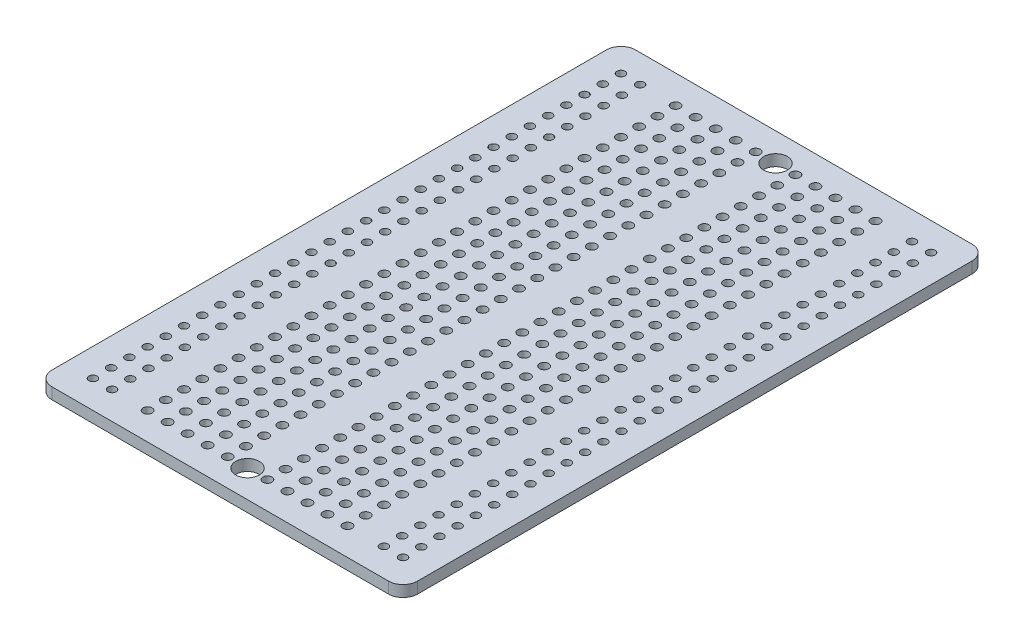
SolidWorks part; units mm, degrees
ref_plane "Front Plane" through (0, 0, 0) normal (0, 0, 1) x (1, 0, 0)
ref_plane "Top Plane" through (0, 0, 0) normal (0, 1, 0) x (1, 0, 0)
ref_plane "Right Plane" through (0, 0, 0) normal (1, 0, 0) x (0, 0, -1)
sketch "Sketch1" plane through (0, 0, 0) normal (0, 1, 0) x (1, 0, 0)
  line L1 (0, 0) -> (51.0032, 0)
  line L2 (0, 0) -> (0, 81.407)
  line L3 (0, 81.407) -> (51.0032, 81.407)
  line L4 (51.0032, 0) -> (51.0032, 81.407)
  dimension "D1" = 81.407
  dimension "D2" = 51.0032
extrude "Boss-Extrude1" add sketch "Sketch1" along normal blind 1.5748
fillet "Fillet1" radius 2.032 4 edges at (0, 0.7874, -81.407) (51.0032, 0.7874, -81.407) (0, 0.7874, 0) (51.0032, 0.7874, 0)
sketch "Sketch2" plane through (0, 1.5748, 0) normal (0, 1, 0) x (1, 0, 0)
  line L0 (3.302, 81.407) -> (3.302, 0) construction
  line L1 (48.9712, 81.407) -> (2.032, 81.407) construction
  line L2 (2.032, 0) -> (48.9712, 0) construction
  line L3 (4.445, 81.407) -> (4.445, 0) construction
  line L4 (5.969, 81.407) -> (5.969, 0) construction
  line L5 (7.112, 81.407) -> (7.112, 0) construction
  line L6 (10.922, 81.407) -> (10.922, 0) construction
  line L7 (12.192, 81.407) -> (12.192, 0) construction
  line L8 (13.716, 81.407) -> (13.716, 0) construction
  line L9 (0, 79.375) -> (0, 2.032) construction
  line L10 (0, 78.105) -> (51.0032, 78.105) construction
  line L11 (51.0032, 2.032) -> (51.0032, 79.375) construction
  line L12 (11.557, 77.47) -> (14.351, 77.47) construction
  line L13 (25.5016, 81.407) -> (25.5016, 0) construction
  line L14 (3.8735, 77.5335) -> (3.8735, 74.9935) construction
  line L15 (25.5016, 5.588) -> (25.5016, 75.819) construction
  line L16 (23.368, 77.47) -> (27.6352, 77.47) construction
  circle A0 centre (3.8735, 77.5335) radius 0.5715
  circle A1 centre (6.5405, 77.5335) radius 0.5715
  circle A2 centre (11.557, 77.47) radius 0.635
  circle A3 centre (14.351, 77.47) radius 0.635
  circle A4 centre (17.145, 77.47) radius 0.635
  circle A5 centre (19.939, 77.47) radius 0.635
  circle A6 centre (22.733, 77.47) radius 0.635
  circle A7 centre (47.1297, 77.5335) radius 0.5715
  circle A8 centre (44.4627, 77.5335) radius 0.5715
  circle A9 centre (39.4462, 77.47) radius 0.635
  circle A10 centre (36.6522, 77.47) radius 0.635
  circle A11 centre (33.8582, 77.47) radius 0.635
  circle A12 centre (31.0642, 77.47) radius 0.635
  circle A13 centre (28.2702, 77.47) radius 0.635
  circle A14 centre (3.8735, 74.9935) radius 0.5715
  circle A15 centre (6.5405, 74.9935) radius 0.5715
  circle A16 centre (11.557, 74.93) radius 0.635
  circle A17 centre (14.351, 74.93) radius 0.635
  circle A18 centre (17.145, 74.93) radius 0.635
  circle A19 centre (19.939, 74.93) radius 0.635
  circle A20 centre (22.733, 74.93) radius 0.635
  circle A21 centre (28.2702, 74.93) radius 0.635
  circle A22 centre (31.0642, 74.93) radius 0.635
  circle A23 centre (33.8582, 74.93) radius 0.635
  circle A24 centre (36.6522, 74.93) radius 0.635
  circle A25 centre (39.4462, 74.93) radius 0.635
  circle A26 centre (44.4627, 74.9935) radius 0.5715
  circle A27 centre (47.1297, 74.9935) radius 0.5715
  circle A28 centre (3.8735, 72.4535) radius 0.5715
  circle A29 centre (6.5405, 72.4535) radius 0.5715
  circle A30 centre (11.557, 72.39) radius 0.635
  circle A31 centre (14.351, 72.39) radius 0.635
  circle A32 centre (17.145, 72.39) radius 0.635
  circle A33 centre (19.939, 72.39) radius 0.635
  circle A34 centre (22.733, 72.39) radius 0.635
  circle A35 centre (28.2702, 72.39) radius 0.635
  circle A36 centre (31.0642, 72.39) radius 0.635
  circle A37 centre (33.8582, 72.39) radius 0.635
  circle A38 centre (36.6522, 72.39) radius 0.635
  circle A39 centre (39.4462, 72.39) radius 0.635
  circle A40 centre (44.4627, 72.4535) radius 0.5715
  circle A41 centre (47.1297, 72.4535) radius 0.5715
  circle A42 centre (3.8735, 69.9135) radius 0.5715
  circle A43 centre (6.5405, 69.9135) radius 0.5715
  circle A44 centre (11.557, 69.85) radius 0.635
  circle A45 centre (14.351, 69.85) radius 0.635
  circle A46 centre (17.145, 69.85) radius 0.635
  circle A47 centre (19.939, 69.85) radius 0.635
  circle A48 centre (22.733, 69.85) radius 0.635
  circle A49 centre (28.2702, 69.85) radius 0.635
  circle A50 centre (31.0642, 69.85) radius 0.635
  circle A51 centre (33.8582, 69.85) radius 0.635
  circle A52 centre (36.6522, 69.85) radius 0.635
  circle A53 centre (39.4462, 69.85) radius 0.635
  circle A54 centre (44.4627, 69.9135) radius 0.5715
  circle A55 centre (47.1297, 69.9135) radius 0.5715
  circle A56 centre (3.8735, 67.3735) radius 0.5715
  circle A57 centre (6.5405, 67.3735) radius 0.5715
  circle A58 centre (11.557, 67.31) radius 0.635
  circle A59 centre (14.351, 67.31) radius 0.635
  circle A60 centre (17.145, 67.31) radius 0.635
  circle A61 centre (19.939, 67.31) radius 0.635
  circle A62 centre (22.733, 67.31) radius 0.635
  circle A63 centre (28.2702, 67.31) radius 0.635
  circle A64 centre (31.0642, 67.31) radius 0.635
  circle A65 centre (33.8582, 67.31) radius 0.635
  circle A66 centre (36.6522, 67.31) radius 0.635
  circle A67 centre (39.4462, 67.31) radius 0.635
  circle A68 centre (44.4627, 67.3735) radius 0.5715
  circle A69 centre (47.1297, 67.3735) radius 0.5715
  circle A70 centre (3.8735, 64.8335) radius 0.5715
  circle A71 centre (6.5405, 64.8335) radius 0.5715
  circle A72 centre (11.557, 64.77) radius 0.635
  circle A73 centre (14.351, 64.77) radius 0.635
  circle A74 centre (17.145, 64.77) radius 0.635
  circle A75 centre (19.939, 64.77) radius 0.635
  circle A76 centre (22.733, 64.77) radius 0.635
  circle A77 centre (28.2702, 64.77) radius 0.635
  circle A78 centre (31.0642, 64.77) radius 0.635
  circle A79 centre (33.8582, 64.77) radius 0.635
  circle A80 centre (36.6522, 64.77) radius 0.635
  circle A81 centre (39.4462, 64.77) radius 0.635
  circle A82 centre (44.4627, 64.8335) radius 0.5715
  circle A83 centre (47.1297, 64.8335) radius 0.5715
  circle A84 centre (3.8735, 62.2935) radius 0.5715
  circle A85 centre (6.5405, 62.2935) radius 0.5715
  circle A86 centre (11.557, 62.23) radius 0.635
  circle A87 centre (14.351, 62.23) radius 0.635
  circle A88 centre (17.145, 62.23) radius 0.635
  circle A89 centre (19.939, 62.23) radius 0.635
  circle A90 centre (22.733, 62.23) radius 0.635
  circle A91 centre (28.2702, 62.23) radius 0.635
  circle A92 centre (31.0642, 62.23) radius 0.635
  circle A93 centre (33.8582, 62.23) radius 0.635
  circle A94 centre (36.6522, 62.23) radius 0.635
  circle A95 centre (39.4462, 62.23) radius 0.635
  circle A96 centre (44.4627, 62.2935) radius 0.5715
  circle A97 centre (47.1297, 62.2935) radius 0.5715
  circle A98 centre (3.8735, 59.7535) radius 0.5715
  circle A99 centre (6.5405, 59.7535) radius 0.5715
  circle A100 centre (11.557, 59.69) radius 0.635
  circle A101 centre (14.351, 59.69) radius 0.635
  circle A102 centre (17.145, 59.69) radius 0.635
  circle A103 centre (19.939, 59.69) radius 0.635
  circle A104 centre (22.733, 59.69) radius 0.635
  circle A105 centre (28.2702, 59.69) radius 0.635
  circle A106 centre (31.0642, 59.69) radius 0.635
  circle A107 centre (33.8582, 59.69) radius 0.635
  circle A108 centre (36.6522, 59.69) radius 0.635
  circle A109 centre (39.4462, 59.69) radius 0.635
  circle A110 centre (44.4627, 59.7535) radius 0.5715
  circle A111 centre (47.1297, 59.7535) radius 0.5715
  circle A112 centre (3.8735, 57.2135) radius 0.5715
  circle A113 centre (6.5405, 57.2135) radius 0.5715
  circle A114 centre (11.557, 57.15) radius 0.635
  circle A115 centre (14.351, 57.15) radius 0.635
  circle A116 centre (17.145, 57.15) radius 0.635
  circle A117 centre (19.939, 57.15) radius 0.635
  circle A118 centre (22.733, 57.15) radius 0.635
  circle A119 centre (28.2702, 57.15) radius 0.635
  circle A120 centre (31.0642, 57.15) radius 0.635
  circle A121 centre (33.8582, 57.15) radius 0.635
  circle A122 centre (36.6522, 57.15) radius 0.635
  circle A123 centre (39.4462, 57.15) radius 0.635
  circle A124 centre (44.4627, 57.2135) radius 0.5715
  circle A125 centre (47.1297, 57.2135) radius 0.5715
  circle A126 centre (3.8735, 54.6735) radius 0.5715
  circle A127 centre (6.5405, 54.6735) radius 0.5715
  circle A128 centre (11.557, 54.61) radius 0.635
  circle A129 centre (14.351, 54.61) radius 0.635
  circle A130 centre (17.145, 54.61) radius 0.635
  circle A131 centre (19.939, 54.61) radius 0.635
  circle A132 centre (22.733, 54.61) radius 0.635
  circle A133 centre (28.2702, 54.61) radius 0.635
  circle A134 centre (31.0642, 54.61) radius 0.635
  circle A135 centre (33.8582, 54.61) radius 0.635
  circle A136 centre (36.6522, 54.61) radius 0.635
  circle A137 centre (39.4462, 54.61) radius 0.635
  circle A138 centre (44.4627, 54.6735) radius 0.5715
  circle A139 centre (47.1297, 54.6735) radius 0.5715
  circle A140 centre (3.8735, 52.1335) radius 0.5715
  circle A141 centre (6.5405, 52.1335) radius 0.5715
  circle A142 centre (11.557, 52.07) radius 0.635
  circle A143 centre (14.351, 52.07) radius 0.635
  circle A144 centre (17.145, 52.07) radius 0.635
  circle A145 centre (19.939, 52.07) radius 0.635
  circle A146 centre (22.733, 52.07) radius 0.635
  circle A147 centre (28.2702, 52.07) radius 0.635
  circle A148 centre (31.0642, 52.07) radius 0.635
  circle A149 centre (33.8582, 52.07) radius 0.635
  circle A150 centre (36.6522, 52.07) radius 0.635
  circle A151 centre (39.4462, 52.07) radius 0.635
  circle A152 centre (44.4627, 52.1335) radius 0.5715
  circle A153 centre (47.1297, 52.1335) radius 0.5715
  circle A154 centre (3.8735, 49.5935) radius 0.5715
  circle A155 centre (6.5405, 49.5935) radius 0.5715
  circle A156 centre (11.557, 49.53) radius 0.635
  circle A157 centre (14.351, 49.53) radius 0.635
  circle A158 centre (17.145, 49.53) radius 0.635
  circle A159 centre (19.939, 49.53) radius 0.635
  circle A160 centre (22.733, 49.53) radius 0.635
  circle A161 centre (28.2702, 49.53) radius 0.635
  circle A162 centre (31.0642, 49.53) radius 0.635
  circle A163 centre (33.8582, 49.53) radius 0.635
  circle A164 centre (36.6522, 49.53) radius 0.635
  circle A165 centre (39.4462, 49.53) radius 0.635
  circle A166 centre (44.4627, 49.5935) radius 0.5715
  circle A167 centre (47.1297, 49.5935) radius 0.5715
  circle A168 centre (3.8735, 47.0535) radius 0.5715
  circle A169 centre (6.5405, 47.0535) radius 0.5715
  circle A170 centre (11.557, 46.99) radius 0.635
  circle A171 centre (14.351, 46.99) radius 0.635
  circle A172 centre (17.145, 46.99) radius 0.635
  circle A173 centre (19.939, 46.99) radius 0.635
  circle A174 centre (22.733, 46.99) radius 0.635
  circle A175 centre (28.2702, 46.99) radius 0.635
  circle A176 centre (31.0642, 46.99) radius 0.635
  circle A177 centre (33.8582, 46.99) radius 0.635
  circle A178 centre (36.6522, 46.99) radius 0.635
  circle A179 centre (39.4462, 46.99) radius 0.635
  circle A180 centre (44.4627, 47.0535) radius 0.5715
  circle A181 centre (47.1297, 47.0535) radius 0.5715
  circle A182 centre (3.8735, 44.5135) radius 0.5715
  circle A183 centre (6.5405, 44.5135) radius 0.5715
  circle A184 centre (11.557, 44.45) radius 0.635
  circle A185 centre (14.351, 44.45) radius 0.635
  circle A186 centre (17.145, 44.45) radius 0.635
  circle A187 centre (19.939, 44.45) radius 0.635
  circle A188 centre (22.733, 44.45) radius 0.635
  circle A189 centre (28.2702, 44.45) radius 0.635
  circle A190 centre (31.0642, 44.45) radius 0.635
  circle A191 centre (33.8582, 44.45) radius 0.635
  circle A192 centre (36.6522, 44.45) radius 0.635
  circle A193 centre (39.4462, 44.45) radius 0.635
  circle A194 centre (44.4627, 44.5135) radius 0.5715
  circle A195 centre (47.1297, 44.5135) radius 0.5715
  circle A196 centre (3.8735, 41.9735) radius 0.5715
  circle A197 centre (6.5405, 41.9735) radius 0.5715
  circle A198 centre (11.557, 41.91) radius 0.635
  circle A199 centre (14.351, 41.91) radius 0.635
  circle A200 centre (17.145, 41.91) radius 0.635
  circle A201 centre (19.939, 41.91) radius 0.635
  circle A202 centre (22.733, 41.91) radius 0.635
  circle A203 centre (28.2702, 41.91) radius 0.635
  circle A204 centre (31.0642, 41.91) radius 0.635
  circle A205 centre (33.8582, 41.91) radius 0.635
  circle A206 centre (36.6522, 41.91) radius 0.635
  circle A207 centre (39.4462, 41.91) radius 0.635
  circle A208 centre (44.4627, 41.9735) radius 0.5715
  circle A209 centre (47.1297, 41.9735) radius 0.5715
  circle A210 centre (3.8735, 39.4335) radius 0.5715
  circle A211 centre (6.5405, 39.4335) radius 0.5715
  circle A212 centre (11.557, 39.37) radius 0.635
  circle A213 centre (14.351, 39.37) radius 0.635
  circle A214 centre (17.145, 39.37) radius 0.635
  circle A215 centre (19.939, 39.37) radius 0.635
  circle A216 centre (22.733, 39.37) radius 0.635
  circle A217 centre (28.2702, 39.37) radius 0.635
  circle A218 centre (31.0642, 39.37) radius 0.635
  circle A219 centre (33.8582, 39.37) radius 0.635
  circle A220 centre (36.6522, 39.37) radius 0.635
  circle A221 centre (39.4462, 39.37) radius 0.635
  circle A222 centre (44.4627, 39.4335) radius 0.5715
  circle A223 centre (47.1297, 39.4335) radius 0.5715
  circle A224 centre (3.8735, 36.8935) radius 0.5715
  circle A225 centre (6.5405, 36.8935) radius 0.5715
  circle A226 centre (11.557, 36.83) radius 0.635
  circle A227 centre (14.351, 36.83) radius 0.635
  circle A228 centre (17.145, 36.83) radius 0.635
  circle A229 centre (19.939, 36.83) radius 0.635
  circle A230 centre (22.733, 36.83) radius 0.635
  circle A231 centre (28.2702, 36.83) radius 0.635
  circle A232 centre (31.0642, 36.83) radius 0.635
  circle A233 centre (33.8582, 36.83) radius 0.635
  circle A234 centre (36.6522, 36.83) radius 0.635
  circle A235 centre (39.4462, 36.83) radius 0.635
  circle A236 centre (44.4627, 36.8935) radius 0.5715
  circle A237 centre (47.1297, 36.8935) radius 0.5715
  circle A238 centre (3.8735, 34.3535) radius 0.5715
  circle A239 centre (6.5405, 34.3535) radius 0.5715
  circle A240 centre (11.557, 34.29) radius 0.635
  circle A241 centre (14.351, 34.29) radius 0.635
  circle A242 centre (17.145, 34.29) radius 0.635
  circle A243 centre (19.939, 34.29) radius 0.635
  circle A244 centre (22.733, 34.29) radius 0.635
  circle A245 centre (28.2702, 34.29) radius 0.635
  circle A246 centre (31.0642, 34.29) radius 0.635
  circle A247 centre (33.8582, 34.29) radius 0.635
  circle A248 centre (36.6522, 34.29) radius 0.635
  circle A249 centre (39.4462, 34.29) radius 0.635
  circle A250 centre (44.4627, 34.3535) radius 0.5715
  circle A251 centre (47.1297, 34.3535) radius 0.5715
  circle A252 centre (3.8735, 31.8135) radius 0.5715
  circle A253 centre (6.5405, 31.8135) radius 0.5715
  circle A254 centre (11.557, 31.75) radius 0.635
  circle A255 centre (14.351, 31.75) radius 0.635
  circle A256 centre (17.145, 31.75) radius 0.635
  circle A257 centre (19.939, 31.75) radius 0.635
  circle A258 centre (22.733, 31.75) radius 0.635
  circle A259 centre (28.2702, 31.75) radius 0.635
  circle A260 centre (31.0642, 31.75) radius 0.635
  circle A261 centre (33.8582, 31.75) radius 0.635
  circle A262 centre (36.6522, 31.75) radius 0.635
  circle A263 centre (39.4462, 31.75) radius 0.635
  circle A264 centre (44.4627, 31.8135) radius 0.5715
  circle A265 centre (47.1297, 31.8135) radius 0.5715
  circle A266 centre (3.8735, 29.2735) radius 0.5715
  circle A267 centre (6.5405, 29.2735) radius 0.5715
  circle A268 centre (11.557, 29.21) radius 0.635
  circle A269 centre (14.351, 29.21) radius 0.635
  circle A270 centre (17.145, 29.21) radius 0.635
  circle A271 centre (19.939, 29.21) radius 0.635
  circle A272 centre (22.733, 29.21) radius 0.635
  circle A273 centre (28.2702, 29.21) radius 0.635
  circle A274 centre (31.0642, 29.21) radius 0.635
  circle A275 centre (33.8582, 29.21) radius 0.635
  circle A276 centre (36.6522, 29.21) radius 0.635
  circle A277 centre (39.4462, 29.21) radius 0.635
  circle A278 centre (44.4627, 29.2735) radius 0.5715
  circle A279 centre (47.1297, 29.2735) radius 0.5715
  circle A280 centre (3.8735, 26.7335) radius 0.5715
  circle A281 centre (6.5405, 26.7335) radius 0.5715
  circle A282 centre (11.557, 26.67) radius 0.635
  circle A283 centre (14.351, 26.67) radius 0.635
  circle A284 centre (17.145, 26.67) radius 0.635
  circle A285 centre (19.939, 26.67) radius 0.635
  circle A286 centre (22.733, 26.67) radius 0.635
  circle A287 centre (28.2702, 26.67) radius 0.635
  circle A288 centre (31.0642, 26.67) radius 0.635
  circle A289 centre (33.8582, 26.67) radius 0.635
  circle A290 centre (36.6522, 26.67) radius 0.635
  circle A291 centre (39.4462, 26.67) radius 0.635
  circle A292 centre (44.4627, 26.7335) radius 0.5715
  circle A293 centre (47.1297, 26.7335) radius 0.5715
  circle A294 centre (3.8735, 24.1935) radius 0.5715
  circle A295 centre (6.5405, 24.1935) radius 0.5715
  circle A296 centre (11.557, 24.13) radius 0.635
  circle A297 centre (14.351, 24.13) radius 0.635
  circle A298 centre (17.145, 24.13) radius 0.635
  circle A299 centre (19.939, 24.13) radius 0.635
  circle A300 centre (22.733, 24.13) radius 0.635
  circle A301 centre (28.2702, 24.13) radius 0.635
  circle A302 centre (31.0642, 24.13) radius 0.635
  circle A303 centre (33.8582, 24.13) radius 0.635
  circle A304 centre (36.6522, 24.13) radius 0.635
  circle A305 centre (39.4462, 24.13) radius 0.635
  circle A306 centre (44.4627, 24.1935) radius 0.5715
  circle A307 centre (47.1297, 24.1935) radius 0.5715
  circle A308 centre (3.8735, 21.6535) radius 0.5715
  circle A309 centre (6.5405, 21.6535) radius 0.5715
  circle A310 centre (11.557, 21.59) radius 0.635
  circle A311 centre (14.351, 21.59) radius 0.635
  circle A312 centre (17.145, 21.59) radius 0.635
  circle A313 centre (19.939, 21.59) radius 0.635
  circle A314 centre (22.733, 21.59) radius 0.635
  circle A315 centre (28.2702, 21.59) radius 0.635
  circle A316 centre (31.0642, 21.59) radius 0.635
  circle A317 centre (33.8582, 21.59) radius 0.635
  circle A318 centre (36.6522, 21.59) radius 0.635
  circle A319 centre (39.4462, 21.59) radius 0.635
  circle A320 centre (44.4627, 21.6535) radius 0.5715
  circle A321 centre (47.1297, 21.6535) radius 0.5715
  circle A322 centre (3.8735, 19.1135) radius 0.5715
  circle A323 centre (6.5405, 19.1135) radius 0.5715
  circle A324 centre (11.557, 19.05) radius 0.635
  circle A325 centre (14.351, 19.05) radius 0.635
  circle A326 centre (17.145, 19.05) radius 0.635
  circle A327 centre (19.939, 19.05) radius 0.635
  circle A328 centre (22.733, 19.05) radius 0.635
  circle A329 centre (28.2702, 19.05) radius 0.635
  circle A330 centre (31.0642, 19.05) radius 0.635
  circle A331 centre (33.8582, 19.05) radius 0.635
  circle A332 centre (36.6522, 19.05) radius 0.635
  circle A333 centre (39.4462, 19.05) radius 0.635
  circle A334 centre (44.4627, 19.1135) radius 0.5715
  circle A335 centre (47.1297, 19.1135) radius 0.5715
  circle A336 centre (3.8735, 16.5735) radius 0.5715
  circle A337 centre (6.5405, 16.5735) radius 0.5715
  circle A338 centre (11.557, 16.51) radius 0.635
  circle A339 centre (14.351, 16.51) radius 0.635
  circle A340 centre (17.145, 16.51) radius 0.635
  circle A341 centre (19.939, 16.51) radius 0.635
  circle A342 centre (22.733, 16.51) radius 0.635
  circle A343 centre (28.2702, 16.51) radius 0.635
  circle A344 centre (31.0642, 16.51) radius 0.635
  circle A345 centre (33.8582, 16.51) radius 0.635
  circle A346 centre (36.6522, 16.51) radius 0.635
  circle A347 centre (39.4462, 16.51) radius 0.635
  circle A348 centre (44.4627, 16.5735) radius 0.5715
  circle A349 centre (47.1297, 16.5735) radius 0.5715
  circle A350 centre (3.8735, 14.0335) radius 0.5715
  circle A351 centre (6.5405, 14.0335) radius 0.5715
  circle A352 centre (11.557, 13.97) radius 0.635
  circle A353 centre (14.351, 13.97) radius 0.635
  circle A354 centre (17.145, 13.97) radius 0.635
  circle A355 centre (19.939, 13.97) radius 0.635
  circle A356 centre (22.733, 13.97) radius 0.635
  circle A357 centre (28.2702, 13.97) radius 0.635
  circle A358 centre (31.0642, 13.97) radius 0.635
  circle A359 centre (33.8582, 13.97) radius 0.635
  circle A360 centre (36.6522, 13.97) radius 0.635
  circle A361 centre (39.4462, 13.97) radius 0.635
  circle A362 centre (44.4627, 14.0335) radius 0.5715
  circle A363 centre (47.1297, 14.0335) radius 0.5715
  circle A364 centre (3.8735, 11.4935) radius 0.5715
  circle A365 centre (6.5405, 11.4935) radius 0.5715
  circle A366 centre (11.557, 11.43) radius 0.635
  circle A367 centre (14.351, 11.43) radius 0.635
  circle A368 centre (17.145, 11.43) radius 0.635
  circle A369 centre (19.939, 11.43) radius 0.635
  circle A370 centre (22.733, 11.43) radius 0.635
  circle A371 centre (28.2702, 11.43) radius 0.635
  circle A372 centre (31.0642, 11.43) radius 0.635
  circle A373 centre (33.8582, 11.43) radius 0.635
  circle A374 centre (36.6522, 11.43) radius 0.635
  circle A375 centre (39.4462, 11.43) radius 0.635
  circle A376 centre (44.4627, 11.4935) radius 0.5715
  circle A377 centre (47.1297, 11.4935) radius 0.5715
  circle A378 centre (3.8735, 8.9535) radius 0.5715
  circle A379 centre (6.5405, 8.9535) radius 0.5715
  circle A380 centre (11.557, 8.89) radius 0.635
  circle A381 centre (14.351, 8.89) radius 0.635
  circle A382 centre (17.145, 8.89) radius 0.635
  circle A383 centre (19.939, 8.89) radius 0.635
  circle A384 centre (22.733, 8.89) radius 0.635
  circle A385 centre (28.2702, 8.89) radius 0.635
  circle A386 centre (31.0642, 8.89) radius 0.635
  circle A387 centre (33.8582, 8.89) radius 0.635
  circle A388 centre (36.6522, 8.89) radius 0.635
  circle A389 centre (39.4462, 8.89) radius 0.635
  circle A390 centre (44.4627, 8.9535) radius 0.5715
  circle A391 centre (47.1297, 8.9535) radius 0.5715
  circle A392 centre (3.8735, 6.4135) radius 0.5715
  circle A393 centre (6.5405, 6.4135) radius 0.5715
  circle A394 centre (11.557, 6.35) radius 0.635
  circle A395 centre (14.351, 6.35) radius 0.635
  circle A396 centre (17.145, 6.35) radius 0.635
  circle A397 centre (19.939, 6.35) radius 0.635
  circle A398 centre (22.733, 6.35) radius 0.635
  circle A399 centre (28.2702, 6.35) radius 0.635
  circle A400 centre (31.0642, 6.35) radius 0.635
  circle A401 centre (33.8582, 6.35) radius 0.635
  circle A402 centre (36.6522, 6.35) radius 0.635
  circle A403 centre (39.4462, 6.35) radius 0.635
  circle A404 centre (44.4627, 6.4135) radius 0.5715
  circle A405 centre (47.1297, 6.4135) radius 0.5715
  circle A406 centre (3.8735, 3.8735) radius 0.5715
  circle A407 centre (6.5405, 3.8735) radius 0.5715
  circle A408 centre (11.557, 3.81) radius 0.635
  circle A409 centre (14.351, 3.81) radius 0.635
  circle A410 centre (17.145, 3.81) radius 0.635
  circle A411 centre (19.939, 3.81) radius 0.635
  circle A412 centre (22.733, 3.81) radius 0.635
  circle A413 centre (28.2702, 3.81) radius 0.635
  circle A414 centre (31.0642, 3.81) radius 0.635
  circle A415 centre (33.8582, 3.81) radius 0.635
  circle A416 centre (36.6522, 3.81) radius 0.635
  circle A417 centre (39.4462, 3.81) radius 0.635
  circle A418 centre (44.4627, 3.8735) radius 0.5715
  circle A419 centre (47.1297, 3.8735) radius 0.5715
  circle A420 centre (25.5016, 77.47) radius 1.651
  circle A421 centre (25.5016, 3.81) radius 1.651
  point P873 (25.5016, 40.7035)
  dimension "D3" = 1.143
  dimension "D13" = 3.302
  dimension "D14" = 3.302
  dimension "D1" = 3.302
  dimension "D2" = 3.302
  dimension "D4" = 1.524
  dimension "D5" = 1.143
  dimension "D6" = 3.81
  dimension "D7" = 1.27
  dimension "D8" = 1.524
  dimension "D10" = 2.794
  dimension "D12" = 2.54
  dimension "D9" = 5
  dimension "D11" = 30
extrude "Cut-Extrude1" cut sketch "Sketch2" against normal through all
